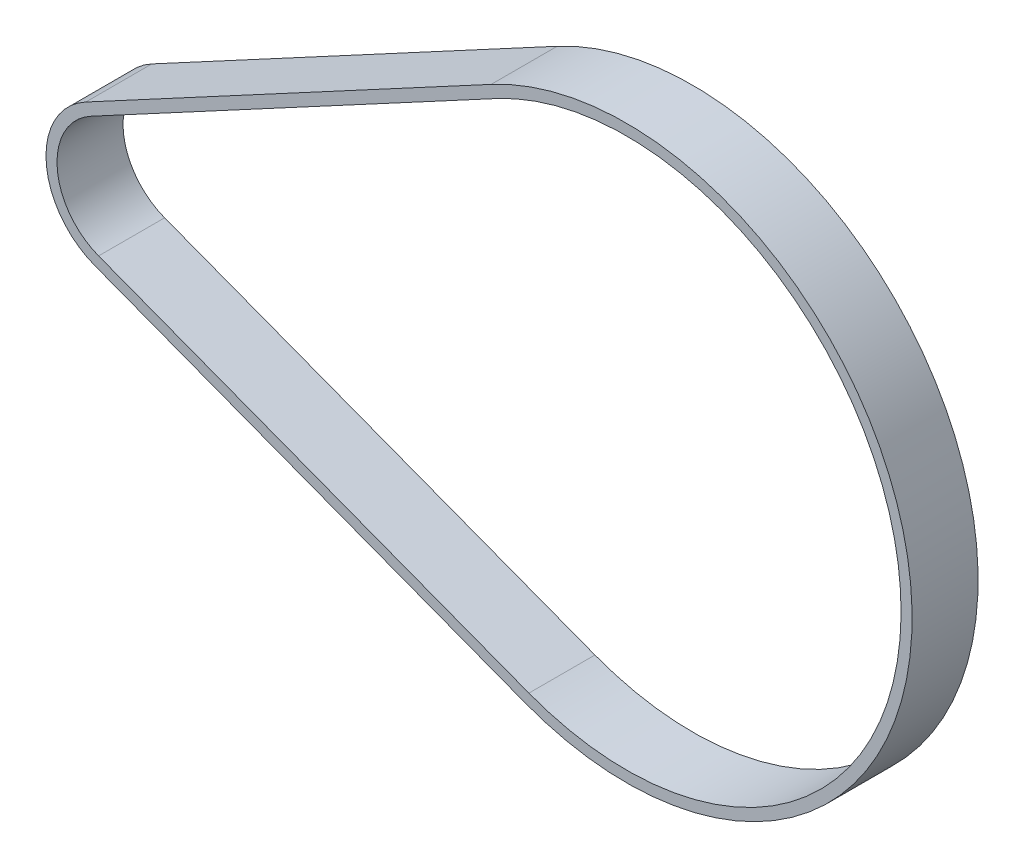
SolidWorks part; units mm, degrees
ref_plane "Front Plane" through (0, 0, 0) normal (0, 0, 1) x (1, 0, 0)
ref_plane "Top Plane" through (0, 0, 0) normal (0, 1, 0) x (1, 0, 0)
ref_plane "Right Plane" through (0, 0, 0) normal (1, 0, 0) x (0, 0, -1)
sketch "Sketch2" plane through (0, 0, 0) normal (0, 0, 1) x (1, 0, 0)
  line L0 (0, 0) -> (1, 0) construction
  line L1 (0, 0) -> (0, 1) construction
  line L4 (36.9486, -24.3097) -> (-2.1662, -9.4493)
  line L5 (-2.9201, 2.1066) -> (33.9323, 21.9232)
  arc A1 (33.9323, 21.9232) -> (36.9486, -24.3097) centre (45.9925, -0.5048) cw
  arc A2 (-2.1662, -9.4493) -> (-2.9201, 2.1066) centre (0.0943, -3.4993) cw
extrude "Extrude-Thin1" add sketch "Sketch2" against normal blind 6 from offset 1.5 thin offset against normal yes thin type mid plane wall 1
